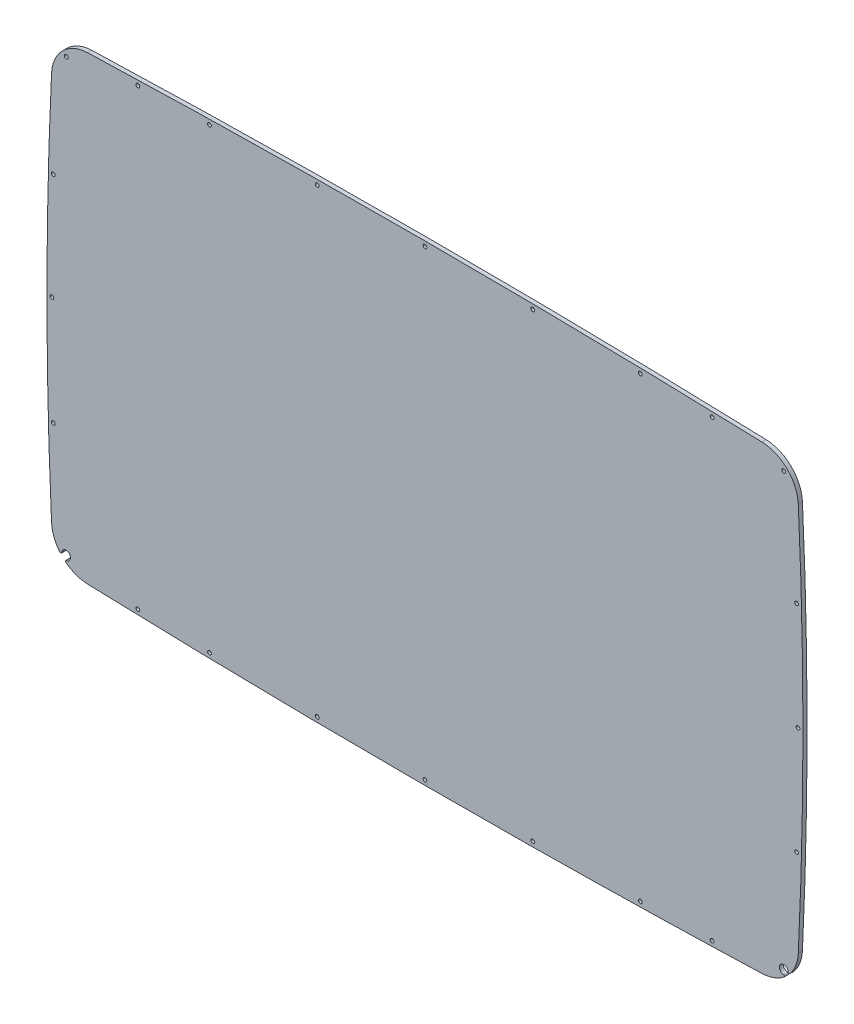
SolidWorks part; units mm, degrees
ref_plane "Front" through (0, 0, 0) normal (0, 0, 1) x (1, 0, 0)
ref_plane "Top" through (0, 0, 0) normal (0, 1, 0) x (1, 0, 0)
ref_plane "Right" through (0, 0, 0) normal (1, 0, 0) x (0, 0, -1)
sketch "Sketch1" plane through (0, 0, 0) normal (0, 0, 1) x (1, 0, 0)
  line L0 (79.622, -180.7786) -> (85.5592, -180.7149)
  line L1 (223.1034, -177.9577) -> (258.4236, -176.8528)
  arc A88 (-274.7298, -169.2696) -> (-275.1845, -170.7425) centre (-274.6747, -170.0932) ccw
  arc A89 (-274.7298, -169.2696) -> (-271.9811, -167.4888) centre (-274.9542, -165.9116) ccw
  arc A90 (-271.9811, -167.4888) -> (-276.5734, -162.9612) centre (-274.9542, -165.9116) ccw
  arc A91 (-276.5734, -162.9612) -> (-278.315, -165.7349) centre (-274.9542, -165.9116) ccw
  arc A92 (-279.7814, -166.2105) -> (-278.315, -165.7349) centre (-279.1394, -165.6916) ccw
  arc A93 (-279.7814, -166.2105) -> (-275.1845, -170.7425) centre (-257.4604, -148.1676) ccw
  arc A94 (275.1845, -170.7425) -> (279.7814, -166.2105) centre (257.4604, -148.1676) ccw
  arc A95 (278.315, -165.7349) -> (279.7814, -166.2105) centre (279.1394, -165.6916) ccw
  arc A96 (278.315, -165.7349) -> (276.5734, -162.9612) centre (274.9542, -165.9116) ccw
  arc A97 (276.5734, -162.9612) -> (271.9811, -167.4888) centre (274.9542, -165.9116) ccw
  arc A98 (271.9811, -167.4888) -> (274.7298, -169.2696) centre (274.9542, -165.9116) ccw
  arc A99 (275.1845, -170.7425) -> (274.7298, -169.2696) centre (274.6747, -170.0932) ccw
  circle A100 centre (-274.9542, 164.9337) radius 1.4351
  circle A101 centre (-284.8103, 82.061) radius 1.4351
  circle A102 centre (-285.9024, 0) radius 1.4351
  circle A103 centre (-284.8103, -83.0389) radius 1.4351
  arc A104 (-258.4236, -176.8528) -> (-223.1034, -177.9577) centre (0, 7519.4009) ccw
  circle A105 centre (-220.0271, -174.2607) radius 1.4351
  circle A106 centre (-165.1, -175.6347) radius 1.4351
  arc A107 (-162.2131, -179.4816) -> (-85.5592, -180.7149) centre (0, 7519.4009) ccw
  arc A108 (-168.1492, -179.3542) -> (-162.2131, -179.4816) centre (0, 7519.4009) ccw
  circle A109 centre (-82.55, -176.963) radius 1.4351
  circle A110 centre (0, -177.4057) radius 1.4351
  circle A111 centre (82.55, -176.963) radius 1.4351
  circle A112 centre (165.1, -175.6347) radius 1.4351
  circle A113 centre (220.0271, -174.2607) radius 1.4351
  circle A114 centre (284.8103, -83.0389) radius 1.4351
  circle A115 centre (285.9024, 0) radius 1.4351
  circle A116 centre (284.8103, 82.061) radius 1.4351
  circle A117 centre (274.9542, 164.9337) radius 1.4351
  circle A118 centre (220.0271, 173.2828) radius 1.4351
  circle A119 centre (165.1, 174.6568) radius 1.4351
  circle A120 centre (82.55, 175.9851) radius 1.4351
  circle A121 centre (0, 176.4278) radius 1.4351
  circle A122 centre (-82.55, 175.9851) radius 1.4351
  circle A123 centre (-220.0271, 173.2828) radius 1.4351
  circle A124 centre (-165.1, 174.6568) radius 1.4351
  arc A125 (-162.2131, 178.5037) -> (-168.1492, 178.3763) centre (0, -7520.3788) ccw
  arc A126 (-85.5592, 179.737) -> (-162.2131, 178.5037) centre (0, -7520.3788) ccw
  arc A127 (-79.622, 179.8007) -> (-85.5592, 179.737) centre (0, -7520.3788) ccw
  arc A128 (-2.9688, 180.2118) -> (-79.622, 179.8007) centre (0, -7520.3788) ccw
  arc A129 (2.9688, 180.2118) -> (-2.9688, 180.2118) centre (0, -7520.3788) ccw
  arc A130 (79.622, 179.8007) -> (2.9688, 180.2118) centre (0, -7520.3788) ccw
  arc A131 (85.5592, 179.737) -> (79.622, 179.8007) centre (0, -7520.3788) ccw
  arc A132 (162.2131, 178.5037) -> (85.5592, 179.737) centre (0, -7520.3788) ccw
  arc A133 (168.1492, 178.3763) -> (162.2131, 178.5037) centre (0, -7520.3788) ccw
  arc A134 (217.1671, 177.1496) -> (168.1492, 178.3763) centre (0, -7520.3788) ccw
  arc A135 (223.1034, 176.9798) -> (217.1671, 177.1496) centre (0, -7520.3788) ccw
  arc A136 (258.4236, 175.8749) -> (223.1034, 176.9798) centre (0, -7520.3788) ccw
  arc A137 (275.1845, 169.7646) -> (258.4236, 175.8749) centre (257.4604, 147.1897) ccw
  arc A138 (279.7814, 165.2326) -> (275.1845, 169.7646) centre (257.4604, 147.1897) ccw
  arc A139 (286.1291, 148.559) -> (279.7814, 165.2326) centre (257.4604, 147.1897) ccw
  arc A140 (288.513, 85.1308) -> (286.1291, 148.559) centre (-2834.64, -0.4889) ccw
  arc A141 (288.6701, 79.1915) -> (288.513, 85.1308) centre (-2834.64, -0.4889) ccw
  arc A142 (289.6845, 2.9713) -> (288.6701, 79.1915) centre (-2834.64, -0.4889) ccw
  arc A143 (289.6854, -2.9701) -> (289.6845, 2.9713) centre (-2834.64, -0.4889) ccw
  arc A144 (288.6701, -80.1694) -> (289.6854, -2.9701) centre (-2834.64, -0.4889) ccw
  arc A145 (288.513, -86.1087) -> (288.6701, -80.1694) centre (-2834.64, -0.4889) ccw
  arc A146 (286.1291, -149.5369) -> (288.513, -86.1087) centre (-2834.64, -0.4889) ccw
  arc A147 (279.7814, -166.2105) -> (286.1291, -149.5369) centre (257.4604, -148.1676) ccw
  arc A148 (275.1845, -170.7425) -> (279.7814, -166.2105) centre (257.4604, -148.1676) ccw
  arc A149 (258.4236, -176.8528) -> (275.1845, -170.7425) centre (257.4604, -148.1676) ccw
  arc A150 (217.1671, -178.1275) -> (223.1034, -177.9577) centre (0, 7519.4009) ccw
  arc A151 (168.1492, -179.3542) -> (217.1671, -178.1275) centre (0, 7519.4009) ccw
  arc A152 (85.5592, -180.7149) -> (162.2131, -179.4816) centre (0, 7519.4009) ccw
  arc A153 (162.2131, -179.4816) -> (168.1492, -179.3542) centre (0, 7519.4009) ccw
  arc A154 (2.9688, -181.1897) -> (79.622, -180.7786) centre (0, 7519.4009) ccw
  arc A155 (-2.9688, -181.1897) -> (2.9688, -181.1897) centre (0, 7519.4009) ccw
  arc A156 (-79.622, -180.7786) -> (-2.9688, -181.1897) centre (0, 7519.4009) ccw
  arc A157 (-85.5592, -180.7149) -> (-79.622, -180.7786) centre (0, 7519.4009) ccw
  arc A158 (-217.1671, -178.1275) -> (-168.1492, -179.3542) centre (0, 7519.4009) ccw
  arc A159 (-223.1034, -177.9577) -> (-217.1671, -178.1275) centre (0, 7519.4009) ccw
  arc A160 (-275.1845, -170.7425) -> (-258.4236, -176.8528) centre (-257.4604, -148.1676) ccw
  arc A161 (-279.7814, -166.2105) -> (-275.1845, -170.7425) centre (-257.4604, -148.1676) ccw
  arc A162 (-286.1291, -149.5369) -> (-279.7814, -166.2105) centre (-257.4604, -148.1676) ccw
  arc A163 (-288.513, -86.1087) -> (-286.1291, -149.5369) centre (2834.64, -0.4889) ccw
  arc A164 (-288.6701, -80.1694) -> (-288.513, -86.1087) centre (2834.64, -0.4889) ccw
  arc A165 (-289.6854, -2.9701) -> (-288.6701, -80.1694) centre (2834.64, -0.4889) ccw
  arc A166 (-289.6845, 2.9713) -> (-289.6854, -2.9701) centre (2834.64, -0.4889) ccw
  arc A167 (-288.6701, 79.1915) -> (-289.6845, 2.9713) centre (2834.64, -0.4889) ccw
  arc A168 (-288.513, 85.1308) -> (-288.6701, 79.1915) centre (2834.64, -0.4889) ccw
  arc A169 (-286.1291, 148.559) -> (-288.513, 85.1308) centre (2834.64, -0.4889) ccw
  arc A170 (-279.7814, 165.2326) -> (-286.1291, 148.559) centre (-257.4604, 147.1897) ccw
  arc A171 (-275.1845, 169.7646) -> (-279.7814, 165.2326) centre (-257.4604, 147.1897) ccw
  arc A172 (-258.4236, 175.8749) -> (-275.1845, 169.7646) centre (-257.4604, 147.1897) ccw
  arc A173 (-223.1034, 176.9798) -> (-258.4236, 175.8749) centre (0, -7520.3788) ccw
  arc A174 (-217.1671, 177.1496) -> (-223.1034, 176.9798) centre (0, -7520.3788) ccw
  arc A175 (-168.1492, 178.3763) -> (-217.1671, 177.1496) centre (0, -7520.3788) ccw
  circle A176 centre (274.9542, -165.9116) radius 1.4351
extrude "Boss-Extrude1" add sketch "Sketch1" along normal blind 3.175 contours A125 A175 A174 A173 A172 A171 A170 A169 A168 A167 A166 A165 A164 A163 A162 A92 A91 A90 A89 A88 A160 A104 A159 A158 A108 A107 A157 A156 A155 A154 L0 A152 A153 A151 A150 L1 A149 A99 A98 A97 A96 A95 A147 A146 A145 A144 A143 A142 A141 A140 A139 region at (-0.0006, -0.4359, 0)
